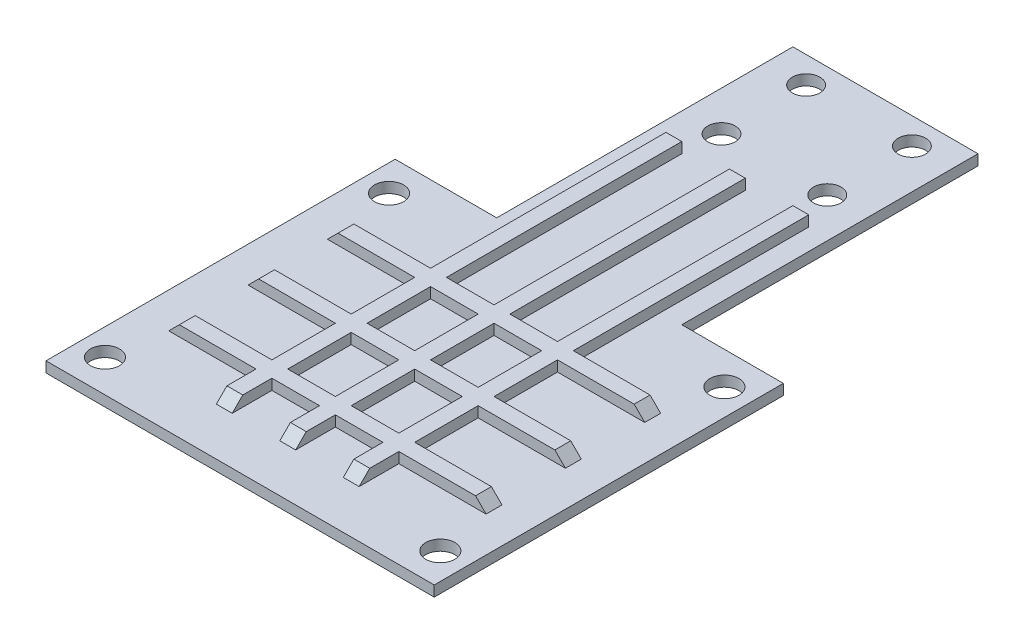
SolidWorks part; units mm, degrees
ref_plane "Front Plane" through (0, 0, 0) normal (0, 0, 1) x (1, 0, 0)
ref_plane "Top Plane" through (0, 0, 0) normal (0, 1, 0) x (1, 0, 0)
ref_plane "Right Plane" through (0, 0, 0) normal (1, 0, 0) x (0, 0, -1)
sketch "Sketch1" plane through (0, 0, 0) normal (0, 1, 0) x (1, 0, 0)
  line L0 (0, -76) -> (0, 76) construction
  line L5 (-17.5, 42.995) -> (-17.5, -42.995)
  line L6 (-31.7, -102.855) -> (31.7, -102.855) construction
  line L11 (-31.7, -102.855) -> (-31.7, -49.145) construction
  line L12 (-31.7, -49.145) -> (31.7, -49.145) construction
  line L13 (31.7, -102.855) -> (31.7, -49.145) construction
  line L14 (0, -49.145) -> (0, -102.855) construction
  line L15 (-31.7, -76) -> (31.7, -76) construction
  line L16 (-31.7, 49.145) -> (31.7, 49.145) construction
  line L17 (-31.7, 49.145) -> (-31.7, 102.855) construction
  line L18 (-31.7, 102.855) -> (31.7, 102.855) construction
  line L19 (31.7, 49.145) -> (31.7, 102.855) construction
  line L20 (0, 102.855) -> (0, 49.145) construction
  line L21 (-31.7, 76) -> (31.7, 76) construction
  line L22 (-36.7, -42.995) -> (-17.5, -42.995)
  line L23 (-36.7, -42.995) -> (-36.7, -109.005)
  line L24 (-36.7, -109.005) -> (36.7, -109.005)
  line L25 (36.7, -42.995) -> (36.7, -109.005)
  line L26 (0, -109.005) -> (0, -32.2076) construction
  line L27 (-36.7, -76) -> (36.7, -76) construction
  line L28 (-36.7, 42.995) -> (-17.5, 42.995)
  line L29 (-36.7, 42.995) -> (-36.7, 109.005)
  line L30 (-36.7, 109.005) -> (36.7, 109.005)
  line L31 (36.7, 42.995) -> (36.7, 109.005)
  line L32 (0, 109.005) -> (0, 37.2379) construction
  line L33 (-36.7, 76) -> (36.7, 76) construction
  line L34 (17.5, -42.995) -> (17.5, 42.995)
  line L35 (17.5, 42.995) -> (36.7, 42.995)
  line L36 (17.5, -42.995) -> (36.7, -42.995)
  circle A4 centre (-31.7, 102.855) radius 2.75
  circle A5 centre (-31.7, 49.145) radius 2.75
  circle A6 centre (31.7, 49.145) radius 2.75
  circle A7 centre (31.7, 102.855) radius 2.75
  circle A8 centre (31.7, -102.855) radius 2.75
  circle A9 centre (31.7, -49.145) radius 2.75
  circle A10 centre (-31.7, -49.145) radius 2.75
  circle A11 centre (-31.7, -102.855) radius 2.75
  point P2 (0, 0)
  point P93 (0, -76)
  point P121 (0, 76)
  point P131 (0, 76)
  point P202 (0, -76)
  dimension "D5" = 5.5
  dimension "D6" = 5.5
  dimension "D7" = 5.5
  dimension "D8" = 5.5
  dimension "D9" = 5.5
  dimension "D10" = 5.5
  dimension "D11" = 5.5
  dimension "D12" = 5.5
  dimension "D1" = 152
  dimension "D2" = 63.4
  dimension "D3" = 53.71
  dimension "D4" = 53.71
  dimension "D13" = 73.4
  dimension "D14" = 66.01
  dimension "D15" = 66.01
  dimension "D16" = 35
extrude "Boss-Extrude1" add sketch "Sketch1" along normal blind 2
sketch "Sketch2" plane through (0, 2, 0) normal (0, 1, 0) x (1, 0, 0)
  line L5 (13.5, 0) -> (10.5, 0)
  line L6 (13.5, 0) -> (13.5, -100)
  line L11 (13.5, -100) -> (10.5, -100)
  line L12 (10.5, 0) -> (10.5, -100)
  line L17 (12, -100) -> (12, 0) construction
  line L18 (13.5, -50) -> (10.5, -50) construction
  line L19 (1.5, 0) -> (-1.5, 0)
  line L20 (1.5, 0) -> (1.5, -100)
  line L21 (1.5, -100) -> (-1.5, -100)
  line L22 (-1.5, 0) -> (-1.5, -100)
  line L23 (0, -100) -> (0, 0) construction
  line L24 (1.5, -50) -> (-1.5, -50) construction
  line L25 (-10.5, 0) -> (-13.5, 0)
  line L26 (-10.5, 0) -> (-10.5, -100)
  line L27 (-10.5, -100) -> (-13.5, -100)
  line L28 (-13.5, 0) -> (-13.5, -100)
  line L29 (-12, -100) -> (-12, 0) construction
  line L30 (-10.5, -50) -> (-13.5, -50) construction
  point P81 (12, -50)
  point P103 (-12, -50)
  point P117 (0, -50)
  dimension "D1" = 3
  dimension "D2" = 3
  dimension "D3" = 3
  dimension "D4" = 100
  dimension "D5" = 12
  dimension "D6" = 12
extrude "Boss-Extrude2" add sketch "Sketch2" along normal blind 2
sketch "Sketch3" plane through (0, 2, 0) normal (0, 1, 0) x (1, 0, 0)
  line L0 (-36.7, -76) -> (36.7, -76) construction
  line L1 (-36.7, -42.995) -> (-36.7, -109.005) construction
  line L2 (36.7, -109.005) -> (36.7, -42.995) construction
  line L4 (-30, -89.5) -> (30, -89.5)
  line L5 (-30, -89.5) -> (-30, -92.5)
  line L6 (-30, -92.5) -> (30, -92.5)
  line L7 (30, -89.5) -> (30, -92.5)
  line L8 (0, -92.5) -> (0, -89.5) construction
  line L9 (-30, -91) -> (30, -91) construction
  line L10 (-30, -59.5) -> (30, -59.5)
  line L11 (-30, -59.5) -> (-30, -62.5)
  line L12 (-30, -62.5) -> (30, -62.5)
  line L13 (30, -59.5) -> (30, -62.5)
  line L14 (0, -62.5) -> (0, -59.5) construction
  line L15 (-30, -61) -> (30, -61) construction
  line L16 (-30, -74.5) -> (30, -74.5)
  line L17 (-30, -74.5) -> (-30, -77.5)
  line L18 (-30, -77.5) -> (30, -77.5)
  line L19 (30, -74.5) -> (30, -77.5)
  line L20 (0, -77.5) -> (0, -74.5) construction
  line L21 (-30, -76) -> (30, -76) construction
  point P16 (0, -76)
  point P87 (0, -76)
  point P112 (0, -61)
  point P122 (0, -91)
  dimension "D1" = 3
  dimension "D2" = 3
  dimension "D3" = 15
  dimension "D4" = 15
  dimension "D5" = 3
  dimension "D6" = 60
extrude "Boss-Extrude3" add sketch "Sketch3" along normal up to surface (2 mm away) up to face at (0, 4, 50)
chamfer "Chamfer1" distance 2 9 edges at (30, 4, 61) (30, 4, 76) (30, 4, 91) (12, 4, 100) (0, 4, 100) (-12, 4, 100) (-30, 4, 91) (-30, 4, 76) (-30, 4, 61)
mirror "Mirror1" about plane through (0, 0, 0) normal (0, 0, 1) of "Chamfer1", "Boss-Extrude3", "Boss-Extrude2"
ref_plane "Plane1" through (0, 0, 0) normal (1, 0, 0) x (0, 0, -1)
sketch "Sketch4" plane through (17.5, 0, 0) normal (1, 0, 0) x (0, 0, -1)
  line L0 (13, 0) -> (13, 2)
  line L1 (-42.995, 0) -> (42.995, 0) construction
  line L2 (-59.5, 2) -> (59.5, 2) construction
  line L3 (13, 2) -> (-15, 2)
  line L4 (-15, 2) -> (-15, 4)
  line L5 (-59.5, 4) -> (59.5, 4) construction
  line L6 (-15, 4) -> (109.005, 4)
  line L7 (109.005, 4) -> (109.005, 0)
  line L8 (109.005, 0) -> (13, 0)
  dimension "D1" = 13
  dimension "D2" = 15
extrude "Cut-Extrude2" cut sketch "Sketch4" against normal through all both and the other way through all
sketch "Sketch5" plane through (0, 2, 0) normal (0, 1, 0) x (1, 0, 0)
  line L0 (-17.5, 13) -> (17.5, 13) construction
  line L1 (-10, -8) -> (10, -8) construction
  line L2 (-10, -8) -> (-10, 8) construction
  line L3 (-10, 8) -> (10, 8) construction
  line L4 (10, -8) -> (10, 8) construction
  line L5 (0, 8) -> (0, -8) construction
  line L6 (-10, 0) -> (10, 0) construction
  circle A0 centre (10, -8) radius 2.6
  circle A1 centre (10, 8) radius 2.6
  circle A2 centre (-10, 8) radius 2.6
  circle A3 centre (-10, -8) radius 2.6
  point P88 (0, 0)
  dimension "D1" = 5.2
  dimension "D2" = 5.2
  dimension "D3" = 5.2
  dimension "D4" = 5.2
  dimension "D5" = 20
  dimension "D6" = 5
extrude "Cut-Extrude3" cut sketch "Sketch5" against normal through all both
equation "\"Reikä\"= 5.5"
equation "\"D5@Sketch1\"=\"Reikä\""
equation "\"D6@Sketch1\"=\"Reikä\""
equation "\"D7@Sketch1\"=\"Reikä\""
equation "\"D8@Sketch1\"=\"Reikä\""
equation "\"D9@Sketch1\"=\"Reikä\""
equation "\"D10@Sketch1\"=\"Reikä\""
equation "\"D11@Sketch1\"=\"Reikä\""
equation "\"D12@Sketch1\"=\"Reikä\""
